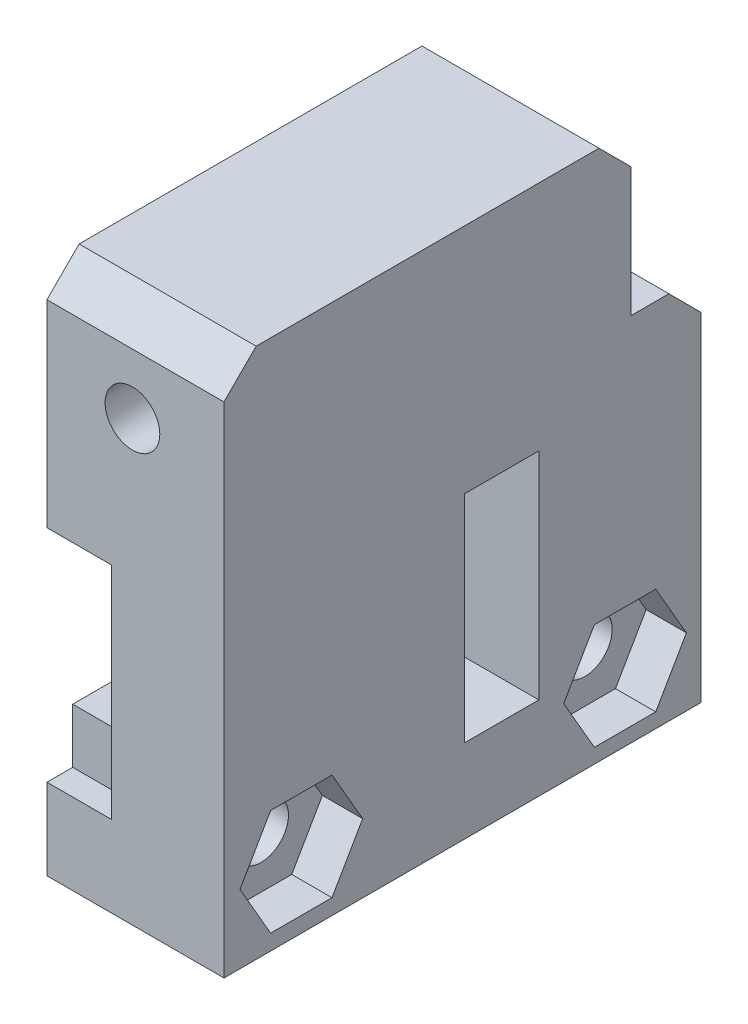
SolidWorks part; units mm, degrees
ref_plane "Front Plane" through (0, 0, 0) normal (0, 0, 1) x (1, 0, 0)
ref_plane "Top Plane" through (0, 0, 0) normal (0, 1, 0) x (1, 0, 0)
ref_plane "Right Plane" through (0, 0, 0) normal (1, 0, 0) x (0, 0, -1)
sketch "Sketch1" plane through (0, 0, 0) normal (1, 0, 0) x (0, 0, -1)
  line L1 (-14.8204, 11.4976) -> (14.8204, 11.4976)
  line L2 (-14.8204, 11.4976) -> (-14.8204, -11.4976)
  line L3 (-14.8204, -11.4976) -> (14.8204, -11.4976)
  line L4 (14.8204, 11.4976) -> (14.8204, -11.4976)
  line L5 (-14.8204, 11.4976) -> (14.8204, -11.4976) construction
  line L6 (-14.8204, -11.4976) -> (14.8204, 11.4976) construction
  point P0 (0, 0)
extrude "Boss-Extrude1" add sketch "Sketch1" along normal blind 11
sketch "Sketch2" plane through (0, 11.4976, 0) normal (0, 1, 0) x (1, 0, 0)
  line L0 (11, 14.8204) -> (11, -14.8204) construction
  line L1 (0, -14.8204) -> (11, -14.8204)
  line L2 (0, -14.8204) -> (0, 10.4797)
  line L3 (0, 10.4797) -> (11, 10.4797)
  line L4 (11, -14.8204) -> (11, 10.4797)
  line L5 (0, -14.8204) -> (11, 10.4797) construction
  line L6 (0, 10.4797) -> (11, -14.8204) construction
  point P0 (5.5, -2.1704)
extrude "Boss-Extrude2" add sketch "Sketch2" along normal blind 10
chamfer "Chamfer1" distance 2 angle 45 3 edges at (5.5, 11.4976, -14.8204) (5.5, 21.4976, -10.4797) (5.5, 21.4976, 14.8204)
sketch "Sketch3" plane through (0, 0, 0) normal (-1, 0, 0) x (0, 0, 1)
  line L1 (-15.4578, 7.2288) -> (15.9867, 7.2288)
  line L2 (-15.4578, 7.2288) -> (-15.4578, -6.4617)
  line L3 (-15.4578, -6.4617) -> (15.9867, -6.4617)
  line L4 (15.9867, 7.2288) -> (15.9867, -6.4617)
  line L5 (-15.4578, 7.2288) -> (15.9867, -6.4617) construction
  line L6 (-15.4578, -6.4617) -> (15.9867, 7.2288) construction
  point P0 (0.2645, 0.3836)
extrude "Cut-Extrude2" cut sketch "Sketch3" against normal blind 4
sketch "Sketch4" plane through (4, 0.4351, 0) normal (-1, 0, 0) x (0, 0, 1)
  line L1 (-10.6052, 3.1028) -> (6.196, 3.1028)
  line L2 (-10.6052, 3.1028) -> (-10.6052, -3.1074)
  line L3 (-10.6052, -3.1074) -> (6.196, -3.1074)
  line L4 (6.196, 3.1028) -> (6.196, -3.1074)
  line L5 (-10.6052, 3.1028) -> (6.196, -3.1074) construction
  line L6 (-10.6052, -3.1074) -> (6.196, 3.1028) construction
  point P0 (-2.2046, -0.0023)
extrude "Boss-Extrude3" add sketch "Sketch4" along normal blind 7
sketch "Sketch5" plane through (0, 0, 6.196) normal (0, 0, 1) x (1, 0, 0)
  circle A0 centre (0.6342, 0.4547) radius 2.041
extrude "Cut-Extrude3" cut sketch "Sketch5" against normal through all contours A0
sketch "Sketch6" plane through (11, 0, 0) normal (1, 0, 0) x (0, 0, -1)
  line L1 (4.7403, 7.0824) -> (0.1188, 7.0824)
  line L2 (4.7403, 7.0824) -> (4.7403, -6.3163)
  line L3 (4.7403, -6.3163) -> (0.1188, -6.3163)
  line L4 (0.1188, 7.0824) -> (0.1188, -6.3163)
  line L5 (4.7403, 7.0824) -> (0.1188, -6.3163) construction
  line L6 (4.7403, -6.3163) -> (0.1188, 7.0824) construction
  point P0 (2.4296, 0.3831)
extrude "Cut-Extrude4" cut sketch "Sketch6" against normal through all contours L4 L3 L2 L1
sketch "Sketch7" plane through (0, 0, 14.8204) normal (0, 0, 1) x (1, 0, 0)
  circle A0 centre (5.3121, 15.7624) radius 1.7
extrude "Cut-Extrude5" cut sketch "Sketch7" against normal blind 27 contours A0
sketch "Sketch15" plane through (11, 0, 0) normal (1, 0, 0) x (0, 0, -1)
  line L1 (-8.1098, -10.532) -> (-6.2046, -7.232)
  line L2 (-6.2046, -7.232) -> (-8.1098, -3.932)
  line L3 (-8.1098, -3.932) -> (-11.9203, -3.932)
  line L4 (-11.9203, -3.932) -> (-13.8256, -7.232)
  line L5 (-13.8256, -7.232) -> (-11.9203, -10.532)
  line L6 (-11.9203, -10.532) -> (-8.1098, -10.532)
  circle A0 centre (-10.0151, -7.232) radius 3.3 construction
sketch "Sketch17" plane through (11, 0, 0) normal (1, 0, 0) x (0, 0, -1)
  line L1 (12.0026, -10.5904) -> (13.9079, -7.2904)
  line L2 (13.9079, -7.2904) -> (12.0026, -3.9904)
  line L3 (12.0026, -3.9904) -> (8.1921, -3.9904)
  line L4 (8.1921, -3.9904) -> (6.2869, -7.2904)
  line L5 (6.2869, -7.2904) -> (8.1921, -10.5904)
  line L6 (8.1921, -10.5904) -> (12.0026, -10.5904)
  circle A0 centre (10.0974, -7.2904) radius 3.3 construction
sketch "Sketch18" plane through (11, 0, 0) normal (1, 0, 0) x (0, 0, -1)
  circle A0 centre (10.0974, -7.2904) radius 1.7
sketch "Sketch19" plane through (11, 0, 0) normal (1, 0, 0) x (0, 0, -1)
  circle A0 centre (-10.0151, -7.232) radius 1.7
sketch "Sketch20" plane through (11, 0, 0) normal (1, 0, 0) x (0, 0, -1)
  line L1 (-13.2201, -3.0643) -> (-6.81, -3.0643)
  line L2 (-13.2201, -3.0643) -> (-13.2201, -11.3998)
  line L3 (-13.2201, -11.3998) -> (-6.81, -11.3998)
  line L4 (-6.81, -3.0643) -> (-6.81, -11.3998)
  line L5 (-13.2201, -3.0643) -> (-6.81, -11.3998) construction
  line L6 (-13.2201, -11.3998) -> (-6.81, -3.0643) construction
  point P0 (-10.0151, -7.232)
sketch "Sketch21" plane through (11, 0, 0) normal (1, 0, 0) x (0, 0, -1)
  line L1 (6.8923, -3.1226) -> (13.3024, -3.1226)
  line L2 (6.8923, -3.1226) -> (6.8923, -11.4581)
  line L3 (6.8923, -11.4581) -> (13.3024, -11.4581)
  line L4 (13.3024, -3.1226) -> (13.3024, -11.4581)
  line L5 (6.8923, -3.1226) -> (13.3024, -11.4581) construction
  line L6 (6.8923, -11.4581) -> (13.3024, -3.1226) construction
  point P0 (10.0974, -7.2904)
extrude "Boss-Extrude4" add sketch "Sketch21" against normal blind 11
extrude "Boss-Extrude5" add sketch "Sketch20" against normal blind 11
extrude "Cut-Extrude6" cut sketch "Sketch15" against normal blind 2.5
extrude "Cut-Extrude7" cut sketch "Sketch19" against normal through all
extrude "Cut-Extrude8" cut sketch "Sketch17" against normal blind 2.5
extrude "Cut-Extrude9" cut sketch "Sketch18" against normal through all
